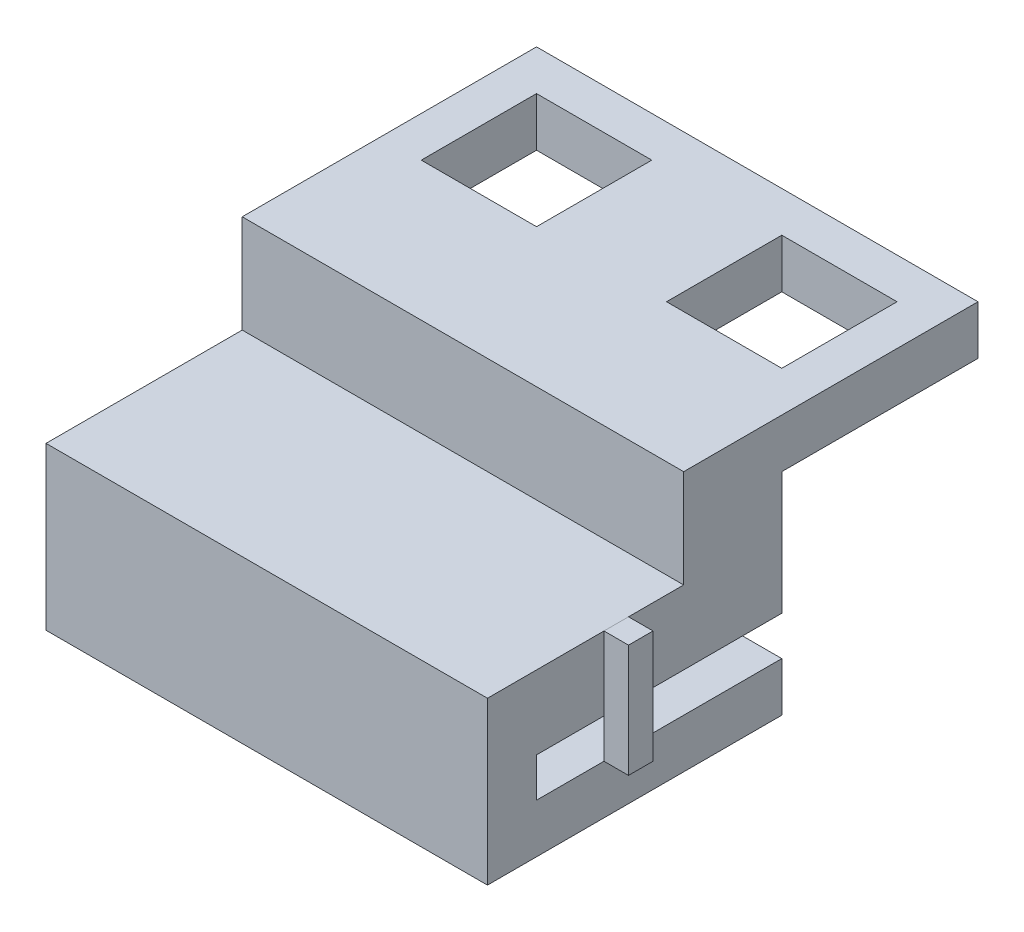
SolidWorks part; units mm, degrees
ref_plane "Front Plane" through (0, 0, 0) normal (0, 0, 1) x (1, 0, 0)
ref_plane "Top Plane" through (0, 0, 0) normal (0, 1, 0) x (1, 0, 0)
ref_plane "Right Plane" through (0, 0, 0) normal (1, 0, 0) x (0, 0, -1)
sketch "Sketch1" plane through (0, 0, 0) normal (0, 1, 0) x (1, 0, 0)
  line L0 (-5, 0) -> (5, 0) construction
  line L1 (-9, 4) -> (9, 4)
  line L2 (-9, 4) -> (-9, -8)
  line L3 (-9, -8) -> (9, -8)
  line L4 (9, 4) -> (9, -8)
  line L6 (-2.65, -2.35) -> (-7.35, -2.35)
  line L7 (-2.65, -2.35) -> (-2.65, 2.35)
  line L8 (-2.65, 2.35) -> (-7.35, 2.35)
  line L9 (-7.35, -2.35) -> (-7.35, 2.35)
  line L10 (-2.65, -2.35) -> (-7.35, 2.35) construction
  line L11 (-2.65, 2.35) -> (-7.35, -2.35) construction
  line L12 (7.35, -2.35) -> (2.65, -2.35)
  line L13 (7.35, -2.35) -> (7.35, 2.35)
  line L14 (7.35, 2.35) -> (2.65, 2.35)
  line L15 (2.65, -2.35) -> (2.65, 2.35)
  line L16 (7.35, -2.35) -> (2.65, 2.35) construction
  line L17 (7.35, 2.35) -> (2.65, -2.35) construction
  circle A0 centre (-5, 0) radius 2.35 construction
  circle A1 centre (5, 0) radius 2.35 construction
  point P8 (0, 0)
  point P9 (0, 4)
  dimension "D3" = 4.7
  dimension "D1" = 10
  dimension "D2" = 18
  dimension "D4" = 12
  dimension "D5" = 4
extrude "Boss-Extrude1" add sketch "Sketch1" along normal blind 2
sketch "Sketch2" plane through (9, 0, 0) normal (1, 0, 0) x (0, 0, -1)
  line L4 (-8, 0) -> (-8, -2)
  line L5 (-8, -2) -> (-16, -2)
  line L6 (-16, -2) -> (-16, -8.6)
  line L8 (-8, 0) -> (4, 0)
  line L9 (4, 0) -> (4, 2)
  line L10 (4, 2) -> (-8, 2)
  line L11 (-8, 2) -> (-8, 0)
  line L12 (-8, 0) -> (4, 0)
  line L13 (4, 0) -> (4, 2)
  line L14 (4, 2) -> (-8, 2)
  line L15 (-8, 2) -> (-8, 0)
  line L16 (-14, -6.6) -> (-14, -5)
  line L17 (-14, -5) -> (-4, -5)
  line L18 (-4, -5) -> (-4, 0)
  line L19 (-4, 0) -> (-8, 0)
  line L20 (-14, -6.6) -> (-4, -6.6)
  line L21 (-4, -6.6) -> (-4, -8.6)
  line L22 (-4, -8.6) -> (-16, -8.6)
  line M10 (-8, 0) -> (4, 0)
  dimension "D2" = 10
  dimension "D3" = 4
  dimension "D4" = 5
  dimension "D5" = 8
  dimension "D6" = 1.6
  dimension "D7" = 3
  dimension "D8" = 2
  dimension "D1" = 0
extrude "Boss-Extrude2" add sketch "Sketch2" against normal up to surface (18 mm away) contours L17 L18 L4 L5 L6 L16 M10 region at (9, -4.7045, 9.7753) up to face at (-9, 1, 2)
sketch "Sketch3" plane through (0, -2, 0) normal (0, 1, 0) x (1, 0, 0)
  line L0 (9, -8) -> (9, -16) construction
  line L1 (9, -10.25) -> (10, -10.25)
  line L2 (9, -10.25) -> (9, -11.25)
  line L3 (9, -11.25) -> (10, -11.25)
  line L4 (10, -10.25) -> (10, -11.25)
  line L6 (7.35, -2.35) -> (7.35, 2.35) construction
  line L7 (-9, -16) -> (-9, -8) construction
  line L8 (-9, -11.25) -> (-10, -11.25)
  line L9 (-9, -11.25) -> (-9, -10.25)
  line L10 (-9, -10.25) -> (-10, -10.25)
  line L11 (-10, -11.25) -> (-10, -10.25)
  point P8 (7.35, 0)
  point P15 (-10.841, -9.409)
  line M7 (9, -16) -> (9, -8)
  dimension "D1" = 1
  dimension "D2" = 1
  dimension "D3" = 10.25
extrude "Boss-Extrude3" add sketch "Sketch3" against normal blind 4.6 separate body contours L4 L1 L3 M7 region at (9.5, -2, 10.75)
